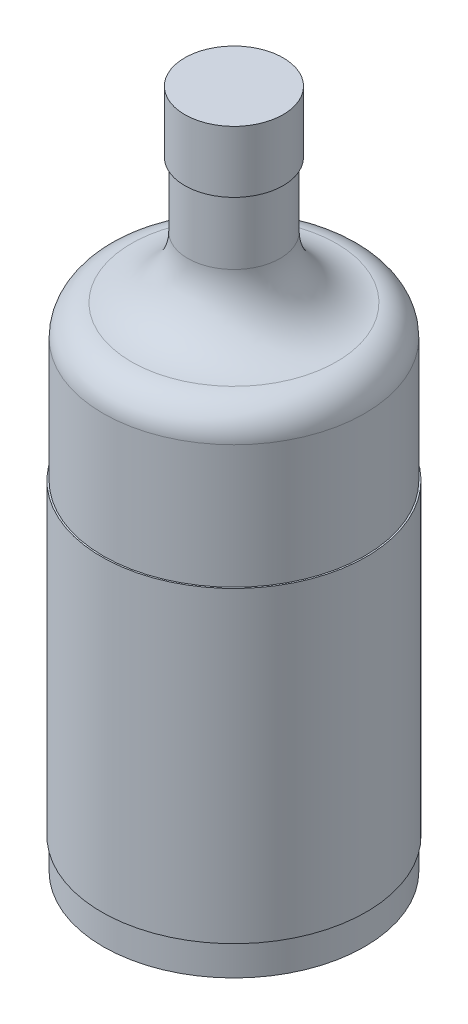
SolidWorks part; units mm, degrees
ref_plane "Front Plane" through (0, 0, 0) normal (0, 0, 1) x (1, 0, 0)
ref_plane "Top Plane" through (0, 0, 0) normal (0, 1, 0) x (1, 0, 0)
ref_plane "Right Plane" through (0, 0, 0) normal (1, 0, 0) x (0, 0, -1)
sketch "Sketch2" plane through (0, 0, 0) normal (0, 1, 0) x (1, 0, 0)
  circle A0 centre (0, 0) radius 42.5
  dimension "D1" = 85
extrude "Boss-Extrude1" add sketch "Sketch2" along normal blind 160
ref_axis "Axis1" through (0, 160, 0) along (0, -1, 0)
sketch "Sketch3" plane through (0, 160, 0) normal (0, 1, 0) x (1, 0, 0)
  circle A0 centre (0, 0) radius 15
  dimension "D1" = 30
extrude "Boss-Extrude2" add sketch "Sketch3" along normal blind 60
fillet "Fillet1" radius 20 1 edges at (0, 160, 15)
fillet "Fillet2" radius 10 1 edges at (0, 160, 42.5)
sketch "Sketch4" plane through (0, 220, 0) normal (0, 1, 0) x (1, 0, 0)
  circle A0 centre (0, 0) radius 16
  circle A1 centre (0, 0) radius 15 construction
  dimension "D1" = 1
extrude "Boss-Extrude3" add sketch "Sketch4" against normal blind 20 from offset 1
sketch "Sketch5" plane through (0, 0, 0) normal (0, -1, 0) x (1, 0, 0)
  circle A0 centre (0, 0) radius 43
  circle A1 centre (0, 0) radius 42.5 construction
  dimension "D1" = 0.5
extrude "Boss-Extrude4" add sketch "Sketch5" against normal blind 100 from offset 10 offset against normal yes
